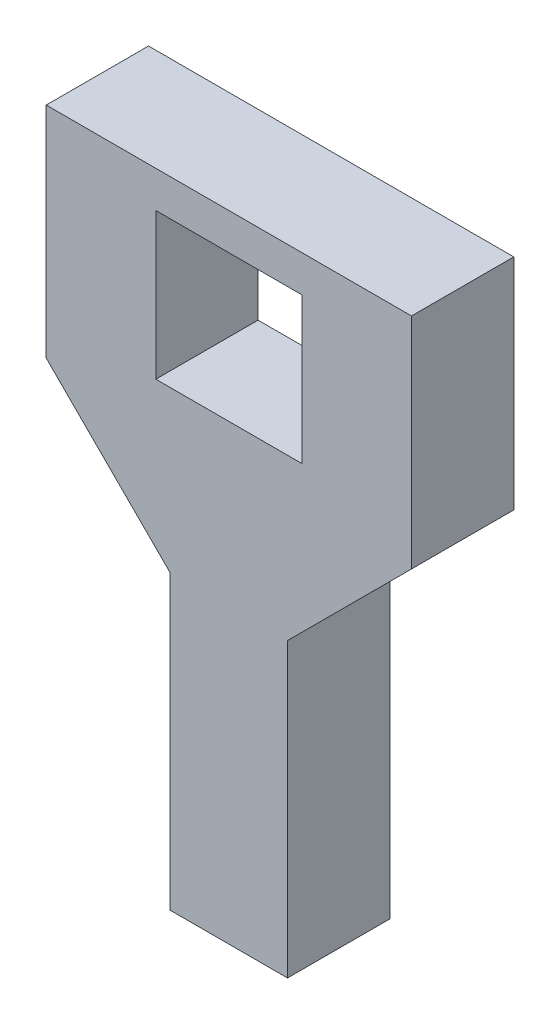
SolidWorks part; units mm, degrees
ref_plane "Alzado" through (0, 0, 0) normal (0, 0, 1) x (1, 0, 0)
ref_plane "Planta" through (0, 0, 0) normal (0, 1, 0) x (1, 0, 0)
ref_plane "Vista lateral" through (0, 0, 0) normal (1, 0, 0) x (0, 0, -1)
sketch "Croquis1" plane through (0, 0, 0) normal (0, 0, 1) x (1, 0, 0)
  line L8 (0, 0) -> (0, -35.9853) construction
  line L13 (-5, 5) -> (5, 5)
  line L19 (-5, 5) -> (-5, -5)
  line L20 (-5, -5) -> (5, -5)
  line L32 (5, 5) -> (5, -5)
  line L37 (-5, 5) -> (5, -5) construction
  line L38 (-5, -5) -> (5, 5) construction
  line L39 (-12.5, 7.5) -> (12.5, 7.5)
  line L40 (-12.5, 7.5) -> (-12.5, -7.5)
  line L41 (-12.5, -7.5) -> (12.5, -7.5)
  line L42 (12.5, 7.5) -> (12.5, -7.5)
  line L43 (-12.5, 7.5) -> (12.5, -7.5) construction
  line L44 (-12.5, -7.5) -> (12.5, 7.5) construction
  line L45 (-12.5, -7.5) -> (-4.0147, -15.9853)
  line L46 (-4.0147, -15.9853) -> (-4.0147, -35.9853)
  line L47 (-4.0147, -35.9853) -> (4.0147, -35.9853)
  line L48 (4.0147, -15.9853) -> (4.0147, -35.9853)
  line L49 (12.5, -7.5) -> (4.0147, -15.9853)
  point P0 (0, 0)
  point P5 (0, 0)
  dimension "D1" = 10
  dimension "D2" = 25
  dimension "D3" = 15
  dimension "D6" = 20
  dimension "D4" = 45
  dimension "D5" = 12
extrude "Saliente-Extruir1" add sketch "Croquis1" along normal blind 7 contours L42 L39 L40 L41 L13 L32 L20 L19 | L49 L41 L45 L46 L47 L48 region at (0, 7.2085, 0) region at (0, -19.0098, 0)
